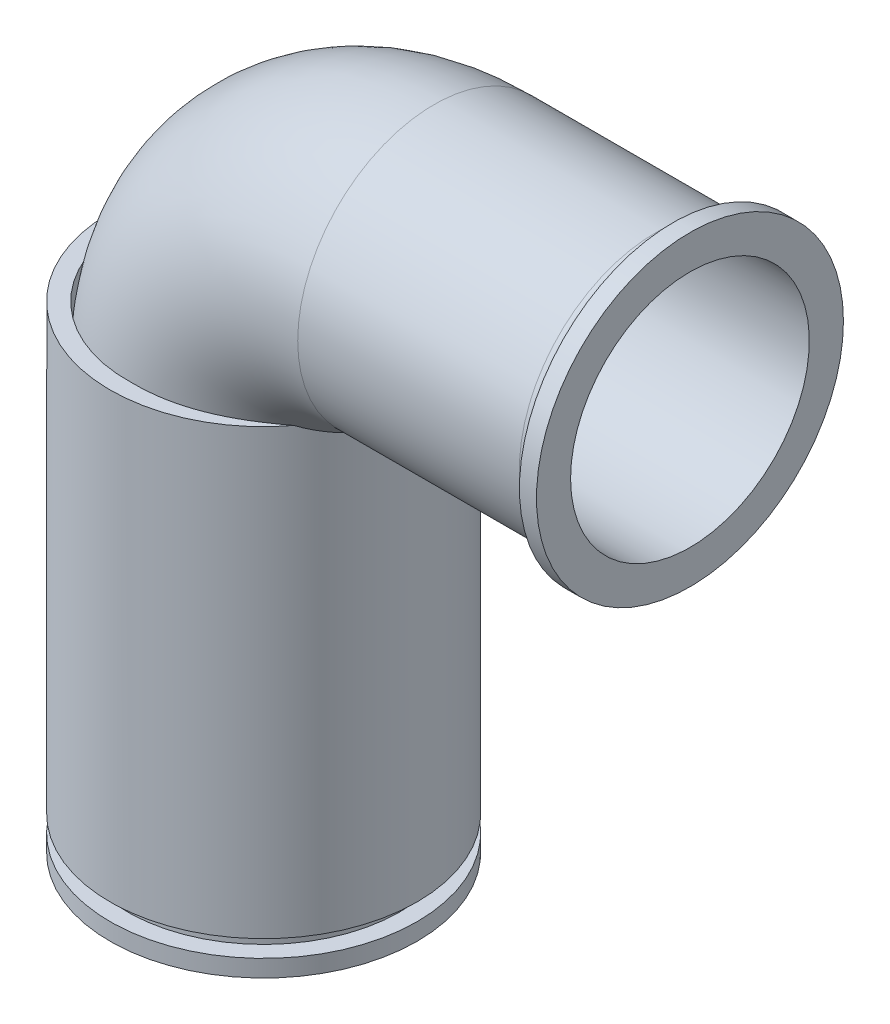
SolidWorks part; units mm, degrees
ref_plane "Front Plane" through (0, 0, 0) normal (0, 0, 1) x (1, 0, 0)
ref_plane "Top Plane" through (0, 0, 0) normal (0, 1, 0) x (1, 0, 0)
ref_plane "Right Plane" through (0, 0, 0) normal (1, 0, 0) x (0, 0, -1)
sketch "Sketch1" plane through (0, 0, 0) normal (0, 0, 1) x (1, 0, 0)
  line L0 (0, -10) -> (0, -35)
  line L1 (10, 0) -> (25, 0)
  arc A0 (0, -10) -> (10, 0) centre (10, -10) cw
  point P6 (0, 0)
  dimension "D3" = 10
  dimension "D1" = 25
  dimension "D2" = 35
sweep "Sweep-Thin6" add path "Sketch1" circular profile diameter 16 parameters "D1"=1, "D3"=16
sketch "Sketch82" plane through (0, -35, 0) normal (0, -1, 0) x (1, 0, 0)
  circle A1 centre (0, 0) radius 9
  circle A2 centre (0, 0) radius 8
  circle A3 centre (0, 0) radius 8
  dimension "D1" = 0
  dimension "D2" = 18
extrude "Boss-Extrude4" add sketch "Sketch82" against normal blind 28
extrude "Cut-Extrude4" cut sketch "Sketch82<2>" against normal blind 1 from offset 1 offset against normal yes
sketch "Sketch82<2>" plane through (0, -35, 0) normal (0, -1, 0) x (1, 0, 0) same geometry as "Sketch82"
sketch "Sketch83" plane through (25, 0, 0) normal (1, 0, 0) x (0, 0, -1)
  circle A0 centre (0, 0) radius 9
  circle A1 centre (0, 0) radius 8 construction
  circle A2 centre (0, 0) radius 8
  dimension "D1" = 18
extrude "Boss-Extrude5" add sketch "Sketch83" against normal blind 1
fillet "Fillet3" radius 1 1 edges at (24, 0, -8)
other "CPoint1" parameters "Diameter"=12.7, "StubLength"=19.05
ref_axis "Axis1" through (0, -45, 0) along (0, 1, 0)
